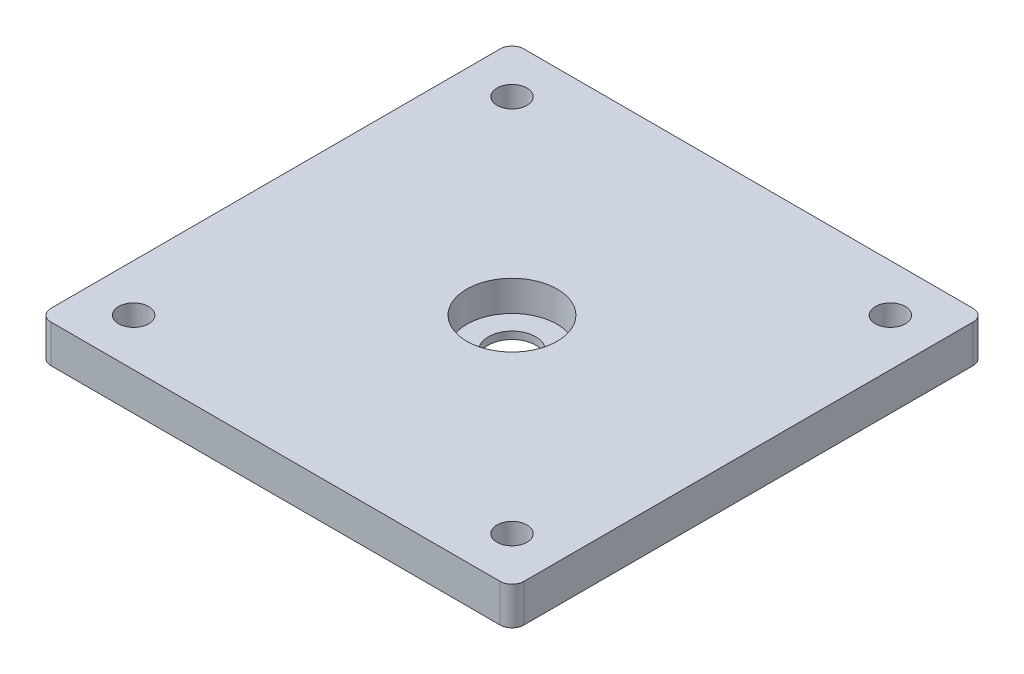
SolidWorks part; units mm, degrees
material "ABS PC"
ref_plane "Front Plane" through (0, 0, 0) normal (0, 0, 1) x (1, 0, 0)
ref_plane "Top Plane" through (0, 0, 0) normal (0, 1, 0) x (1, 0, 0)
ref_plane "Right Plane" through (0, 0, 0) normal (1, 0, 0) x (0, 0, -1)
sketch "Sketch1" plane through (0, 0, 0) normal (0, 1, 0) x (1, 0, 0)
  line L1 (-41.199, 52.7578) -> (38.801, 52.7578)
  line L2 (-51.199, 42.7578) -> (-51.199, -37.2422)
  line L3 (-41.199, -47.2422) -> (38.801, -47.2422)
  line L4 (48.801, 42.7578) -> (48.801, -37.2422)
  arc A0 (-41.199, 52.7578) -> (-51.199, 42.7578) centre (-41.199, 42.7578) ccw
  arc A1 (-51.199, -37.2422) -> (-41.199, -47.2422) centre (-41.199, -37.2422) ccw
  arc A2 (38.801, -47.2422) -> (48.801, -37.2422) centre (38.801, -37.2422) ccw
  arc A3 (48.801, 42.7578) -> (38.801, 52.7578) centre (38.801, 42.7578) ccw
  circle A4 centre (0, 0) radius 6.35
  circle A5 centre (0, 0) radius 12.7
  circle A6 centre (-41.199, 42.7578) radius 3.175
  circle A7 centre (38.801, 42.7578) radius 3.175
  circle A8 centre (38.801, -37.2422) radius 3.175
  circle A9 centre (-41.199, -37.2422) radius 3.175
  point P6 (-51.199, 52.7578)
  point P9 (-51.199, -47.2422)
  point P14 (48.801, 52.7578)
  dimension "D3" = 10
  dimension "D4" = 12.7
  dimension "D5" = 25.4
  dimension "D6" = 6.35
  dimension "D7" = 6.35
  dimension "D8" = 6.35
  dimension "D9" = 6.35
  dimension "D1" = 100
  dimension "D2" = 100
extrude "Boss-Extrude1" add sketch "Sketch1" along normal blind 10 contours L4 A3 L1 A0 L2 A1 L3 A2 A5 region at (-1.199, 0, -51.3436)
extrude "Boss-Extrude2" add sketch "Sketch1<3>" along normal blind 2.5 contours A5 A4 region at (-12.3408, 0, 0)
sketch "Sketch1<3>" plane through (0, 0, 0) normal (0, 1, 0) x (1, 0, 0) same geometry as "Sketch1"
sketch "Sketch2" plane through (0, 10, 0) normal (0, 1, 0) x (1, 0, 0)
  line L4 (48.801, -37.2422) -> (48.801, 42.7578)
  line L5 (38.801, 52.7578) -> (-41.199, 52.7578)
  line L6 (-51.199, 42.7578) -> (-51.199, -37.2422)
  line L7 (-41.199, -47.2422) -> (38.801, -47.2422)
  line L8 (48.801, -37.2422) -> (48.801, 42.7578)
  line L9 (38.801, 52.7578) -> (-41.199, 52.7578)
  line L10 (-51.199, 42.7578) -> (-51.199, -37.2422)
  line L11 (-41.199, -47.2422) -> (38.801, -47.2422)
  circle A0 centre (0, 0) radius 12.7
  circle A1 centre (0, 0) radius 12.7 construction
  arc A4 (48.801, 42.7578) -> (38.801, 52.7578) centre (38.801, 42.7578) ccw
  arc A5 (-41.199, 52.7578) -> (-51.199, 42.7578) centre (-41.199, 42.7578) ccw
  arc A6 (-51.199, -37.2422) -> (-41.199, -47.2422) centre (-41.199, -37.2422) ccw
  arc A7 (38.801, -47.2422) -> (48.801, -37.2422) centre (38.801, -37.2422) ccw
  arc A8 (48.801, 42.7578) -> (38.801, 52.7578) centre (38.801, 42.7578) ccw
  arc A9 (-41.199, 52.7578) -> (-51.199, 42.7578) centre (-41.199, 42.7578) ccw
  arc A10 (-51.199, -37.2422) -> (-41.199, -47.2422) centre (-41.199, -37.2422) ccw
  arc A11 (38.801, -47.2422) -> (48.801, -37.2422) centre (38.801, -37.2422) ccw
  dimension "D1" = 0
extrude "Boss-Extrude3" add sketch "Sketch2" against normal through all contours A0
sketch "Sketch3" plane through (0, 10, 0) normal (0, 1, 0) x (1, 0, 0)
  line L0 (-51.199, 2.7578) -> (3.0728, 2.7578) construction
  line L1 (-1.199, 52.7578) -> (-1.199, 2.7578) construction
  line L4 (48.801, -37.2422) -> (48.801, 42.7578)
  line L5 (38.801, 52.7578) -> (-41.199, 52.7578)
  line L6 (-51.199, 42.7578) -> (-51.199, -37.2422)
  line L7 (-41.199, -47.2422) -> (38.801, -47.2422)
  line L8 (48.801, -37.2422) -> (48.801, 42.7578)
  line L9 (38.801, 52.7578) -> (-41.199, 52.7578)
  line L10 (-51.199, 42.7578) -> (-51.199, -37.2422)
  line L11 (-41.199, -47.2422) -> (38.801, -47.2422)
  circle A1 centre (-1.199, 2.7578) radius 5
  arc A4 (48.801, 42.7578) -> (38.801, 52.7578) centre (38.801, 42.7578) ccw
  arc A5 (-41.199, 52.7578) -> (-51.199, 42.7578) centre (-41.199, 42.7578) ccw
  arc A6 (-51.199, -37.2422) -> (-41.199, -47.2422) centre (-41.199, -37.2422) ccw
  arc A7 (38.801, -47.2422) -> (48.801, -37.2422) centre (38.801, -37.2422) ccw
  arc A8 (48.801, 42.7578) -> (38.801, 52.7578) centre (38.801, 42.7578) ccw
  arc A9 (-41.199, 52.7578) -> (-51.199, 42.7578) centre (-41.199, 42.7578) ccw
  arc A10 (-51.199, -37.2422) -> (-41.199, -47.2422) centre (-41.199, -37.2422) ccw
  arc A11 (38.801, -47.2422) -> (48.801, -37.2422) centre (38.801, -37.2422) ccw
  dimension "D2" = 10
  dimension "D1" = 0
extrude "Cut-Extrude3" cut sketch "Sketch3" against normal blind 10 contours A1
sketch "Sketch4" plane through (0, 10, 0) normal (0, 1, 0) x (1, 0, 0)
  circle A1 centre (-1.199, 2.7578) radius 10
  dimension "D1" = 20
extrude "Cut-Extrude4" cut sketch "Sketch4" against normal blind 5 from offset 1.45 offset against normal yes
sketch "Sketch6" plane through (0, 0, 0) normal (0, -1, 0) x (1, 0, 0)
  line L4 (48.801, -42.7578) -> (48.801, 37.2422)
  line L5 (38.801, 47.2422) -> (-41.199, 47.2422)
  line L6 (-51.199, 37.2422) -> (-51.199, -42.7578)
  line L7 (-41.199, -52.7578) -> (38.801, -52.7578)
  line L8 (48.801, -42.7578) -> (48.801, 37.2422)
  line L9 (38.801, 47.2422) -> (-41.199, 47.2422)
  line L10 (-51.199, 37.2422) -> (-51.199, -42.7578)
  line L11 (-41.199, -52.7578) -> (38.801, -52.7578)
  arc A4 (48.801, 37.2422) -> (38.801, 47.2422) centre (38.801, 37.2422) ccw
  arc A5 (-41.199, 47.2422) -> (-51.199, 37.2422) centre (-41.199, 37.2422) ccw
  arc A6 (-51.199, -42.7578) -> (-41.199, -52.7578) centre (-41.199, -42.7578) ccw
  arc A7 (38.801, -52.7578) -> (48.801, -42.7578) centre (38.801, -42.7578) ccw
  arc A8 (48.801, 37.2422) -> (38.801, 47.2422) centre (38.801, 37.2422) ccw
  arc A9 (-41.199, 47.2422) -> (-51.199, 37.2422) centre (-41.199, 37.2422) ccw
  arc A10 (-51.199, -42.7578) -> (-41.199, -52.7578) centre (-41.199, -42.7578) ccw
  arc A11 (38.801, -52.7578) -> (48.801, -42.7578) centre (38.801, -42.7578) ccw
  dimension "D1" = 0
extrude "Cut-Extrude5" cut sketch "Sketch6" against normal blind 2
sketch "Sketch7" plane through (0, 10, 0) normal (0, 1, 0) x (1, 0, 0)
  circle A0 centre (-1.199, 2.7578) radius 10
  circle A1 centre (-1.199, 2.7578) radius 5 construction
  dimension "D1" = 20
extrude "Cut-Extrude7" cut sketch "Sketch7" against normal up to surface (6.45 mm away) up to face at (-1.199, 3.55, 7.2422)
sketch "Sketch8" plane through (0, 3.55, 0) normal (0, 1, 0) x (1, 0, 0)
  circle A0 centre (-1.199, 2.7578) radius 9.5625
  circle A1 centre (-1.199, 2.7578) radius 10 construction
  circle A2 centre (-1.199, 2.7578) radius 10
  dimension "D1" = 19.125
extrude "Boss-Extrude4" add sketch "Sketch8" along normal up to surface (6.45 mm away) up to face at (-1.199, 10, 7.2422)
sketch "Sketch9" plane through (0, 10, 0) normal (0, 1, 0) x (1, 0, 0)
  line L0 (-51.199, 42.7578) -> (-51.199, 52.7578)
  line L1 (-51.199, 52.7578) -> (-41.199, 52.7578)
  line L2 (38.801, 52.7578) -> (48.801, 52.7578)
  line L3 (48.801, 52.7578) -> (48.801, 42.7578)
  line L4 (-51.199, -37.2422) -> (-51.199, -47.2422)
  line L5 (-51.199, -47.2422) -> (-41.199, -47.2422)
  line L6 (48.801, -37.2422) -> (48.801, -47.2422)
  line L7 (48.801, -47.2422) -> (38.801, -47.2422)
  arc A0 (-51.199, -37.2422) -> (-41.199, -47.2422) centre (-41.199, -37.2422) ccw construction
  arc A1 (38.801, -47.2422) -> (48.801, -37.2422) centre (38.801, -37.2422) ccw construction
  arc A2 (48.801, 42.7578) -> (38.801, 52.7578) centre (38.801, 42.7578) ccw construction
  arc A3 (-41.199, 52.7578) -> (-51.199, 42.7578) centre (-41.199, 42.7578) ccw construction
  arc A4 (-51.199, -37.2422) -> (-41.199, -47.2422) centre (-41.199, -37.2422) ccw
  arc A5 (38.801, -47.2422) -> (48.801, -37.2422) centre (38.801, -37.2422) ccw
  arc A6 (48.801, 42.7578) -> (38.801, 52.7578) centre (38.801, 42.7578) ccw
  arc A7 (-41.199, 52.7578) -> (-51.199, 42.7578) centre (-41.199, 42.7578) ccw
extrude "Boss-Extrude5" add sketch "Sketch9" against normal up to surface (8 mm away) up to face at (-41.199, 2, -45.9328)
fillet "Fillet1" radius 2.5 4 edges at (-51.199, 6, 47.2422) (48.801, 6, 47.2422) (48.801, 6, -52.7578) (-51.199, 6, -52.7578)
